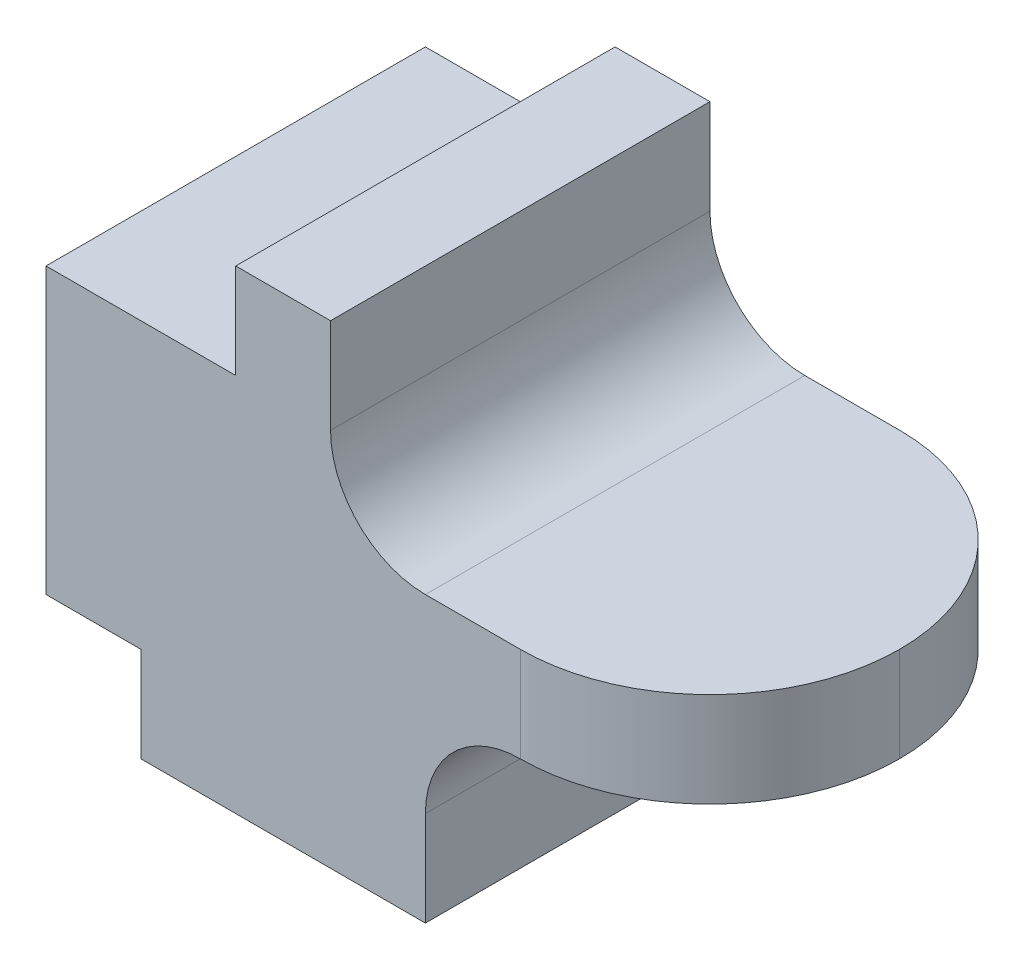
SolidWorks part; units mm, degrees
ref_plane "前基準面" through (0, 0, 0) normal (0, 0, 1) x (1, 0, 0)
ref_plane "上基準面" through (0, 0, 0) normal (0, 1, 0) x (1, 0, 0)
ref_plane "右基準面" through (0, 0, 0) normal (1, 0, 0) x (0, 0, -1)
sketch "草圖1" plane through (0, 0, 0) normal (0, 0, 1) x (1, 0, 0)
  line L0 (0, 0) -> (0, 15)
  line L1 (0, 15) -> (10, 15)
  line L2 (10, 15) -> (10, 20)
  line L3 (10, 20) -> (15, 20)
  line L4 (15, 20) -> (15, 10)
  line L5 (15, 10) -> (35, 10)
  line L6 (35, 10) -> (35, 5)
  line L7 (35, 5) -> (20, 5)
  line L8 (20, 5) -> (20, -5)
  line L9 (20, -5) -> (5, -5)
  line L10 (5, -5) -> (5, 0)
  line L11 (5, 0) -> (0, 0)
  point P3 (0, 7.5)
  dimension "D1" = 15
  dimension "D2" = 5
  dimension "D3" = 5
  dimension "D4" = 5
  dimension "D5" = 5
  dimension "D6" = 10
  dimension "D7" = 5
  dimension "D8" = 15
  dimension "D9" = 15
  dimension "D10" = 35
extrude "填料-伸長1" add sketch "草圖1" along normal blind 20
fillet "圓角2" radius 10 2 edges at (35, 7.5, 0) (35, 7.5, 20)
fillet "圓角1" radius 5 2 edges at (20, 5, 10) (15, 10, 10)
